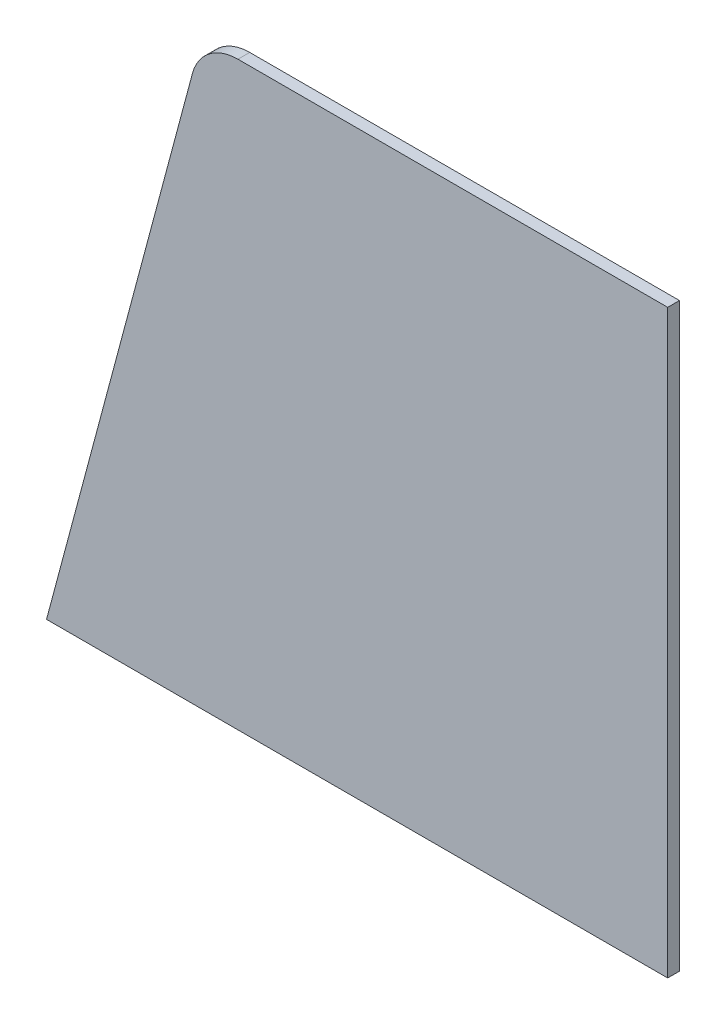
SolidWorks part; units mm, degrees
material "Balsa"
ref_plane "Front Plane" through (0, 0, 0) normal (0, 0, 1) x (1, 0, 0)
ref_plane "Top Plane" through (0, 0, 0) normal (0, 1, 0) x (1, 0, 0)
ref_plane "Right Plane" through (0, 0, 0) normal (1, 0, 0) x (0, 0, -1)
sketch "Sketch1" plane through (0, 0, 0) normal (0, 0, 1) x (1, 0, 0)
  line L0 (0, 0) -> (335.28, 0)
  line L1 (335.28, 0) -> (335.28, 313.5173)
  line L2 (335.28, 313.5173) -> (103.3213, 313.5173)
  line L3 (78.7832, 294.6776) -> (0, 0)
  arc A0 (103.3213, 313.5173) -> (78.7832, 294.6776) centre (103.3213, 288.1173) ccw
  point P3 (0, 0)
  point P4 (335.28, 313.5173)
  point P8 (83.82, 313.5173)
  point P11 (335.28, 313.5173)
  point P12 (333.7164, 313.5173)
  dimension "D4" = 25.4
  dimension "D1" = 335.28
  dimension "D2" = 313.5173
  dimension "D3" = 251.46
extrude "Boss-Extrude1" add sketch "Sketch1" along normal blind 6.35
